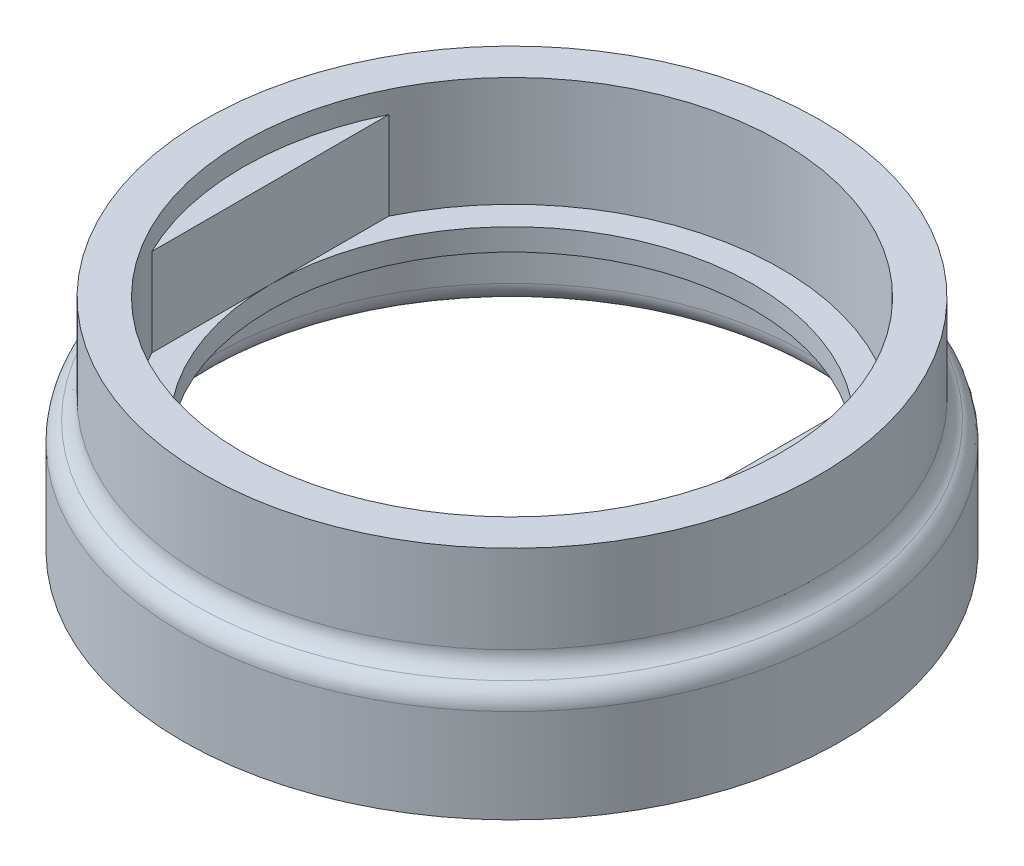
SolidWorks part; units mm, degrees
material "ABS"
ref_plane "前视基准面" through (0, 0, 0) normal (0, 0, 1) x (1, 0, 0)
ref_plane "上视基准面" through (0, 0, 0) normal (0, 1, 0) x (1, 0, 0)
ref_plane "右视基准面" through (0, 0, 0) normal (1, 0, 0) x (0, 0, -1)
sketch "草图1" plane through (0, 0, 0) normal (0, 1, 0) x (1, 0, 0)
  circle A0 centre (0, 0) radius 12.25
  circle A1 centre (0, 0) radius 14
  dimension "D1" = 24.5
  dimension "D2" = 28
extrude "凸台-拉伸1" add sketch "草图1" along normal blind 5
sketch "草图2" plane through (0, 0, 0) normal (0, 1, 0) x (1, 0, 0)
  line L0 (-14, 0) -> (14, 0) construction
  line L1 (0, 14) -> (0, -14) construction
  line L2 (-11, 5.391) -> (-11, -5.391)
  line L3 (11, 5.391) -> (11, -5.391)
  circle A0 centre (0, 0) radius 14 construction
  circle A1 centre (0, 0) radius 12.25 construction
  arc A2 (-11, 5.391) -> (-11, -5.391) centre (0, 0) ccw
  arc A3 (11, 5.391) -> (11, -5.391) centre (0, 0) cw
  dimension "D1" = 22
extrude "凸台-拉伸2" add sketch "草图2" along normal blind 4
sketch "草图3" plane through (0, 0, 0) normal (0, 1, 0) x (1, 0, 0)
  circle A0 centre (0, 0) radius 13.5
  circle A1 centre (0, 0) radius 15
  dimension "D1" = 27
  dimension "D2" = 30
extrude "凸台-拉伸3" add sketch "草图3" against normal blind 5
fillet "圆角2" radius 1 1 edges at (0, 0, 14)
fillet "圆角3" radius 1 1 edges at (0, 0, 15)
sketch "草图4" plane through (0, 0, 0) normal (0, -1, 0) x (1, 0, 0)
  circle A0 centre (0, 0) radius 13.5
  circle A1 centre (0, 0) radius 11
extrude "凸台-拉伸4" add sketch "草图4" along normal blind 1
fillet "圆角5" radius 1 1 edges at (0, -5, 13.5)
